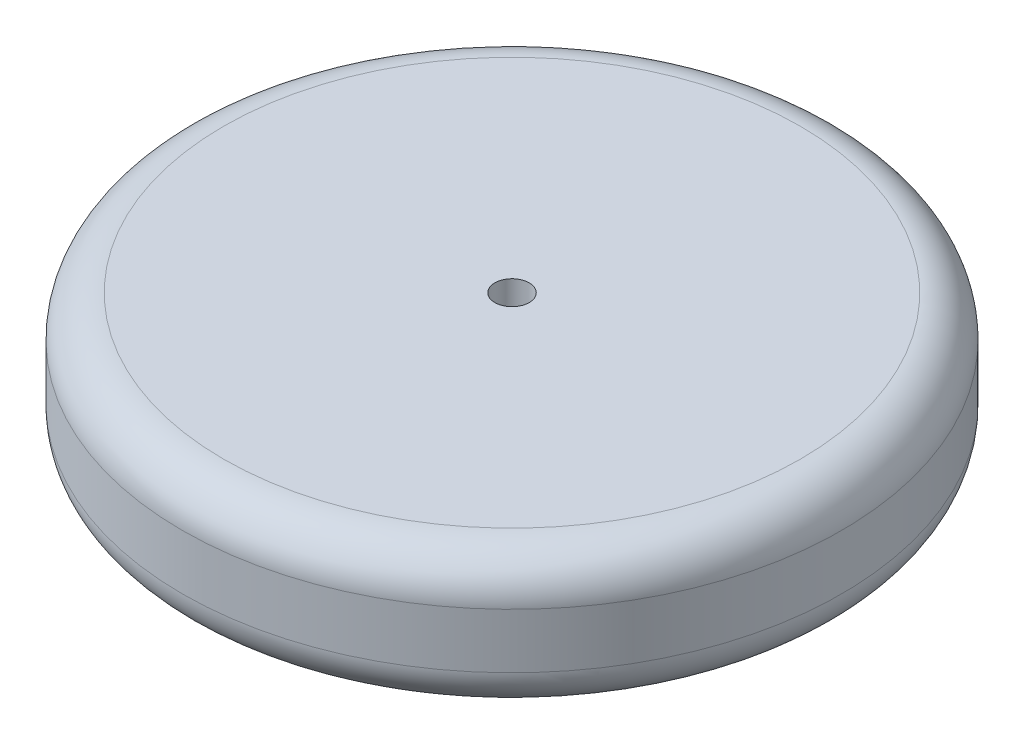
SolidWorks part; units mm, degrees
ref_plane "Front Plane" through (0, 0, 0) normal (0, 0, 1) x (1, 0, 0)
ref_plane "Top Plane" through (0, 0, 0) normal (0, 1, 0) x (1, 0, 0)
ref_plane "Right Plane" through (0, 0, 0) normal (1, 0, 0) x (0, 0, -1)
sketch "Sketch1" plane through (0, 0, 0) normal (0, 1, 0) x (1, 0, 0)
  circle A0 centre (0, 0) radius 304.8
  dimension "D1" = 609.6
extrude "Boss-Extrude1" add sketch "Sketch1" along normal blind 127
fillet "Fillet1" radius 38.1 2 edges at (0, 0, 304.8) (0, 127, 304.8)
sketch "Sketch2" plane through (0, 127, 0) normal (0, 1, 0) x (1, 0, 0)
  circle A0 centre (0, 0) radius 15.875
  dimension "D1" = 31.75
extrude "Cut-Extrude1" cut sketch "Sketch2" against normal through all
